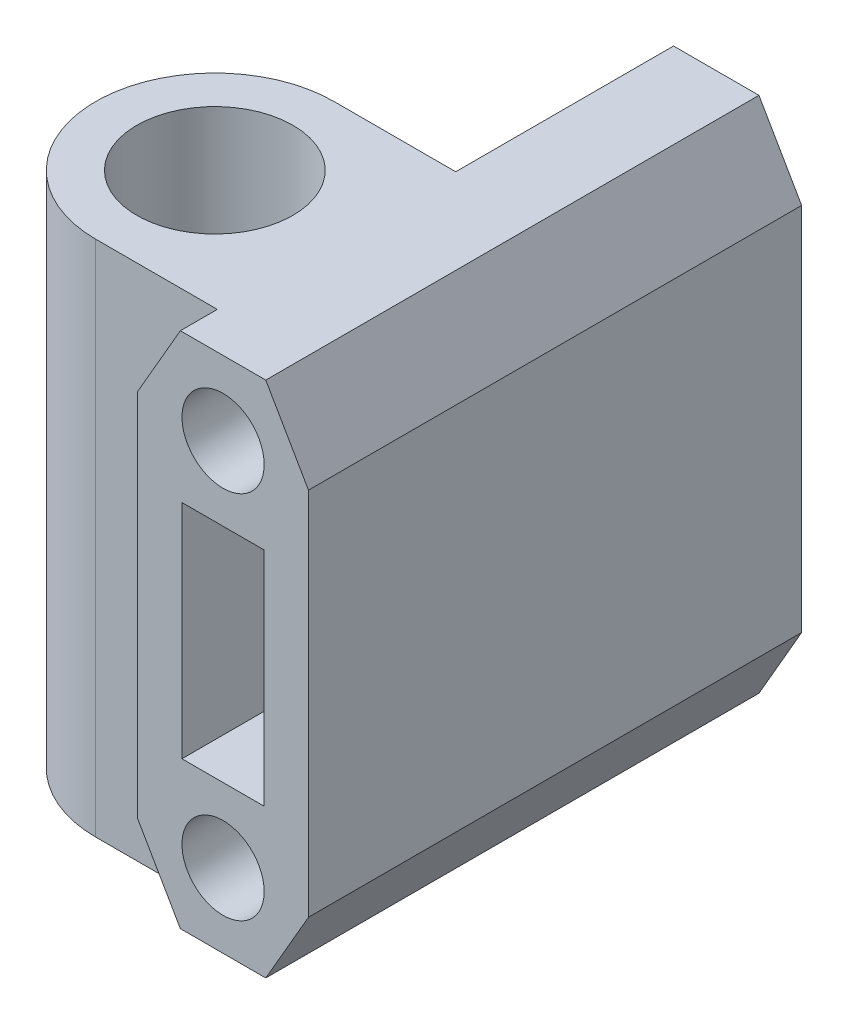
SolidWorks part; units mm, degrees
ref_plane "Front Plane" through (0, 0, 0) normal (0, 0, 1) x (1, 0, 0)
ref_plane "Top Plane" through (0, 0, 0) normal (0, 1, 0) x (1, 0, 0)
ref_plane "Right Plane" through (0, 0, 0) normal (1, 0, 0) x (0, 0, -1)
sketch "Sketch1" plane through (0, 0, 0) normal (0, 0, 1) x (1, 0, 0)
  line L0 (-10.3923, 22.5) -> (-10.3923, -22.5)
  line L1 (10.3923, 22.5) -> (5.1962, 31.5)
  line L2 (5.1962, 31.5) -> (-5.1962, 31.5)
  line L3 (-5.1962, 31.5) -> (-10.3923, 22.5)
  line L5 (-5, 13.5) -> (5, 13.5)
  line L8 (5, -13.5) -> (-5, -13.5)
  line L10 (-10.3923, -22.5) -> (-5.1962, -31.5)
  line L11 (-5.1962, -31.5) -> (5.1962, -31.5)
  line L12 (5.1962, -31.5) -> (10.3923, -22.5)
  line L13 (-5, 13.5) -> (-5, -13.5)
  line L14 (5, 13.5) -> (5, -13.5)
  line L15 (10.3923, 22.5) -> (10.3923, -22.5)
  line L17 (7.7942, 18) -> (10.3923, 22.5) [skipped]
  line L18 (-10.3923, 22.5) -> (-7.7942, 18) [skipped]
  line L19 (-7.7942, -18) -> (-10.3923, -22.5) [skipped]
  line L20 (10.3923, -22.5) -> (7.7942, -18) [skipped]
  circle A0 centre (0, 22.5) radius 5
  circle A1 centre (0, -22.5) radius 5
  circle A2 centre (0, 22.5) radius 9 construction
  circle A3 centre (0, -22.5) radius 9 construction
  dimension "D1" = 45
  dimension "D3" = 10
  dimension "D4" = 4
  dimension "D2" = 22.5
  dimension "D5" = 10
  dimension "D6" = 5
extrude "Boss-Extrude1" add sketch "Sketch1" along normal blind 60
sketch "Sketch2" plane through (0, -31.5, 0) normal (0, -1, 0) x (1, 0, 0)
  line L1 (-10.3923, 0) -> (-5.1962, 0) construction
  line L2 (-5.1962, 0) -> (5.1962, 0) construction
  line L3 (-20, 25) -> (-5.1962, 25)
  line L4 (-5.1962, 60) -> (-5.1962, 0) construction
  line L5 (-5.1962, 25) -> (-5.1962, 0)
  line L6 (-5.1962, 0) -> (-20, 0)
  circle A0 centre (-20, 12.5) radius 4.5
  arc A1 (-20, 25) -> (-20, 0) centre (-20, 12.5) ccw
  dimension "D1" = 9
  dimension "D4" = 8
  dimension "D2" = 20
  dimension "D3" = 0
  dimension "D5" = 12.5
extrude "Boss-Extrude2" add sketch "Sketch2" against normal up to surface (18 mm away) up to face at (0, -13.5, 30)
sketch "Sketch3" plane through (0, -13.5, 0) normal (0, 1, 0) x (1, 0, 0)
  line L1 (-16.2472, -6) -> (-23.7528, -6)
  line L2 (-23.7528, -6) -> (-27.5056, -12.5)
  line L3 (-27.5056, -12.5) -> (-23.7528, -19)
  line L4 (-23.7528, -19) -> (-16.2472, -19)
  line L5 (-16.2472, -19) -> (-12.4944, -12.5)
  line L6 (-12.4944, -12.5) -> (-16.2472, -6)
  circle A0 centre (-20, -12.5) radius 6.5 construction
  dimension "D1" = 13
extrude "Cut-Extrude1" cut sketch "Sketch3" against normal blind 7
sketch "Sketch4" plane through (0, -31.5, 0) normal (0, -1, 0) x (1, 0, 0)
  line L0 (-20, 12.5) -> (-20, 41) construction
  line L1 (-20, 55.5) -> (-5.1962, 55.5)
  line L2 (-5.1962, 60) -> (-5.1962, 25) construction
  line L3 (-5.1962, 55.5) -> (-5.1962, 26.5)
  line L4 (-5.1962, 26.5) -> (-20, 26.5)
  circle A0 centre (-20, 41) radius 9.5
  arc A1 (-20, 55.5) -> (-20, 26.5) centre (-20, 41) ccw
  dimension "D1" = 19
  dimension "D2" = 5
  dimension "D3" = 28.5
extrude "Boss-Extrude3" add sketch "Sketch4" against normal up to surface (63 mm away) up to face at (0, 31.5, 30)
